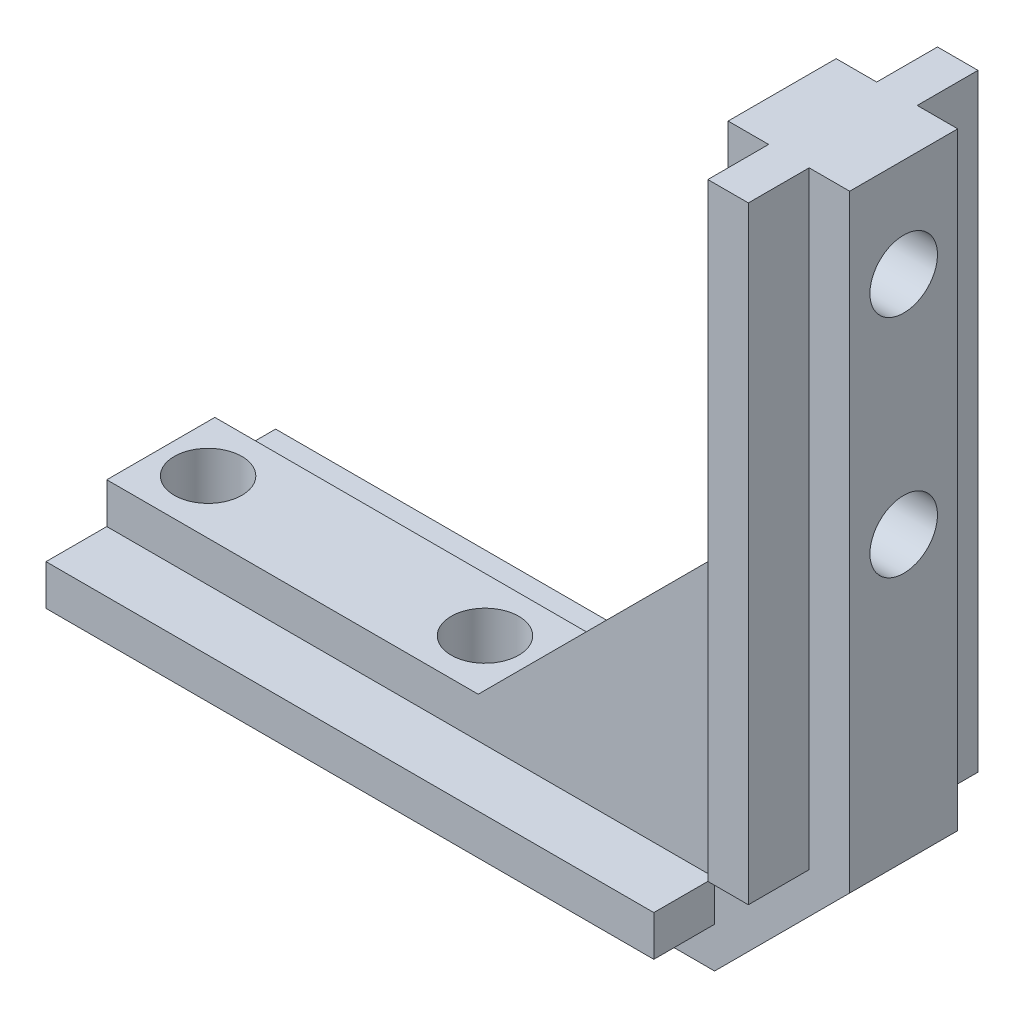
SolidWorks part; units mm, degrees
note: The reader was unsure of these and kept them because the rebuilt part matched: shared geometry of "Sketch3<2>".
ref_plane "Front Plane" through (0, 0, 0) normal (0, 0, 1) x (1, 0, 0)
ref_plane "Top Plane" through (0, 0, 0) normal (0, 1, 0) x (1, 0, 0)
ref_plane "Right Plane" through (0, 0, 0) normal (1, 0, 0) x (0, 0, -1)
sketch "Sketch2" plane through (0, 0, 0) normal (0, 0, 1) x (1, 0, 0)
  line L0 (0, 0) -> (45, 0)
  line L1 (55, 10) -> (55, 55)
  line L2 (55, 10) -> (45, 0)
  line L3 (55, 55) -> (46, 55)
  line L4 (46, 55) -> (46, 27.5)
  line L5 (27.5, 9) -> (0, 9)
  line L6 (0, 9) -> (0, 0)
  line L7 (46, 27.5) -> (27.5, 9)
  dimension "D1" = 55
  dimension "D2" = 55
  dimension "D3" = 9
  dimension "D4" = 9
  dimension "D5" = 45
  dimension "D6" = 45
  dimension "D7" = 27.5
  dimension "D8" = 10
extrude "Boss-Extrude1" add sketch "Sketch2" along normal mid plane 8
sketch "Sketch3" plane through (0, 0, 4) normal (0, 0, 1) x (1, 0, 0)
  line L1 (0, 6) -> (45, 6)
  line L2 (0, 6) -> (0, 3)
  line L3 (0, 3) -> (45, 3)
  line L4 (45, 6) -> (45, 3)
  line L5 (49, 55) -> (52, 55)
  line L6 (49, 55) -> (49, 10)
  line L7 (49, 10) -> (52, 10)
  line L8 (0, 9) -> (0, 0)
  line L9 (0, 0) -> (45, 0)
  line L10 (45, 0) -> (55, 10)
  line L11 (55, 10) -> (55, 55)
  line L12 (55, 55) -> (46, 55)
  line L13 (46, 55) -> (46, 27.5)
  line L14 (46, 27.5) -> (27.5, 9)
  line L15 (27.5, 9) -> (0, 9)
  line L16 (0, 9) -> (0, 0) construction
  line L17 (0, 0) -> (45, 0) construction
  line L18 (45, 0) -> (55, 10) construction
  line L19 (55, 10) -> (55, 55) construction
  line L20 (55, 55) -> (46, 55) construction
  line L21 (46, 55) -> (46, 27.5) construction
  line L22 (46, 27.5) -> (27.5, 9) construction
  line L23 (27.5, 9) -> (0, 9) construction
  line L24 (52, 55) -> (52, 10)
  point P10 (0, 4.5)
  point P12 (50.5, 55)
  point P14 (45, 4.5)
  point P19 (0, 0)
  point P20 (50.5, 10)
  dimension "D2" = 3
  dimension "D3" = 3
  dimension "D1" = 0
extrude "Boss-Extrude2" add sketch "Sketch3" along normal blind 4.5
extrude "Boss-Extrude3" add sketch "Sketch3<2>" against normal blind 4.5 from surface at -8
sketch "Sketch3<2>" plane through (0, 0, 4) normal (0, 0, 1) x (1, 0, 0) same geometry as "Sketch3"
sketch "Sketch4" plane through (46, 0, 0) normal (-1, 0, 0) x (0, 0, 1)
  line L0 (0, 55) -> (0, 27.5) construction
  line L1 (4, 55) -> (-4, 55) construction
  line L2 (4, 27.5) -> (-4, 27.5) construction
  line L3 (-4, 51.19) -> (4, 51.19) construction
  line L4 (-4, 55) -> (-4, 27.5) construction
  line L5 (4, 55) -> (4, 27.5) construction
  circle A0 centre (0, 47.69) radius 2.5
  circle A1 centre (0, 31) radius 2.5
  point P12 (0, 47.69)
  point P14 (0, 31)
  dimension "D2" = 5
  dimension "D3" = 5
  dimension "D1" = 3.81
  dimension "D4" = 3.5
  dimension "D5" = 3.5
hole_wizard "Tap Drill for M6x1.0 Tap1" positions "Sketch4" profile "Sketch5" hole size "M6x1.0" standard "ANSI Metric" end condition through all
sketch "Sketch5" plane through (46, 31, 0) normal (0, 1, 0) x (0, 0, 1)
  line L0 (0, 0) -> (0, 9)
  line L1 (0, 9) -> (2.5, 9)
  line L2 (2.5, 9) -> (2.5, 0)
  line L5 (2.5, 0) -> (0, 0)
  line L11 (0, -6.35) -> (0, 107.95) construction
  dimension "Thru Hole Dia." = 5
  dimension "Thru Hole Depth" = 9
sketch "Sketch6" plane through (0, 9, 0) normal (0, 1, 0) x (1, 0, 0)
  line L0 (0, 0) -> (27.5, 0) construction
  line L3 (0, -4) -> (0, 4) construction
  line L6 (27.5, -4) -> (27.5, 4) construction
  line L7 (0, -4) -> (0, 4) construction
  line L8 (45, 4) -> (0, 4) construction
  line L9 (0, 8.5) -> (0, 4) construction
  circle A0 centre (3.5, 0) radius 2.5
  circle A1 centre (24, 0) radius 2.5
  point P12 (3.5, 0)
  point P14 (24, 0)
  point P26 (3.5, 0)
  point P28 (24, 0)
  dimension "D2" = 5
  dimension "D3" = 5
  dimension "D1" = 3.5
  dimension "D4" = 3.5
hole_wizard "Tap Drill for M6x1.0 Tap2" positions "Sketch6" profile "Sketch7" hole size "M6x1.0" standard "ANSI Metric" end condition through all
sketch "Sketch7" plane through (24, 9, 0) normal (1, 0, 0) x (0, 0, 1)
  line L0 (0, 0) -> (0, 9)
  line L1 (0, 9) -> (2.5, 9)
  line L2 (2.5, 9) -> (2.5, 0)
  line L5 (2.5, 0) -> (0, 0)
  line L11 (0, -6.35) -> (0, 107.95) construction
  dimension "Thru Hole Dia." = 5
  dimension "Thru Hole Depth" = 9
